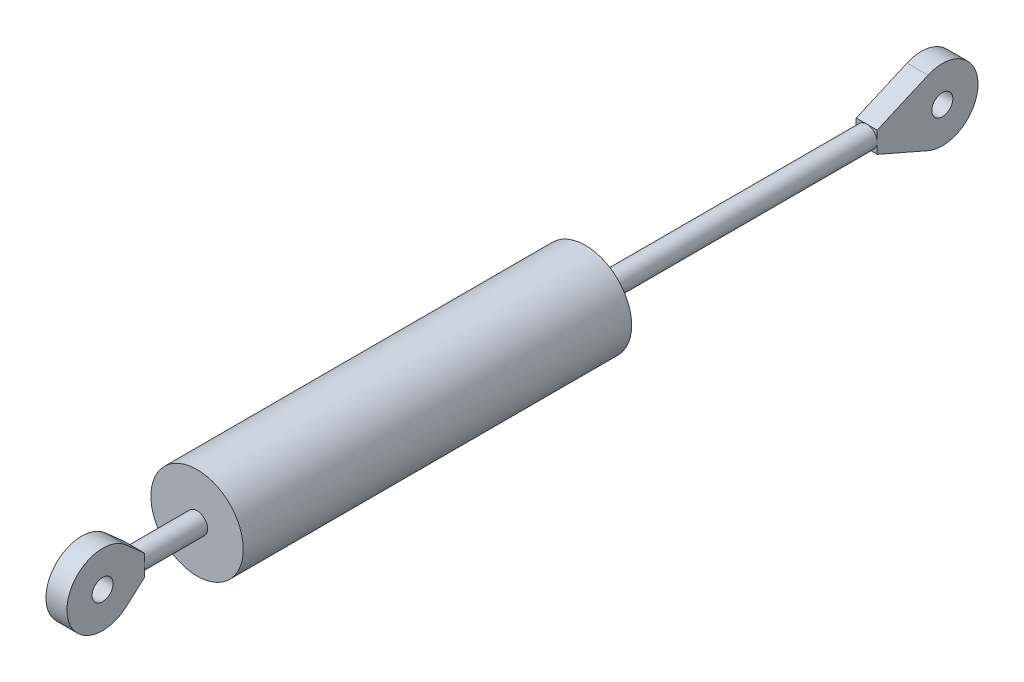
SolidWorks part; units mm, degrees
ref_plane "Front Plane" through (0, 0, 0) normal (0, 0, 1) x (1, 0, 0)
ref_plane "Top Plane" through (0, 0, 0) normal (0, 1, 0) x (1, 0, 0)
ref_plane "Right Plane" through (0, 0, 0) normal (1, 0, 0) x (0, 0, -1)
sketch "Sketch1" plane through (0, 0, 0) normal (1, 0, 0) x (0, 0, -1)
  line L0 (-46.25, 0) -> (46.25, 0)
  line L1 (-46.25, 11) -> (46.25, 11)
  line L2 (-46.25, 11) -> (-46.25, 0)
  line L4 (46.25, 11) -> (46.25, 0)
  line L5 (-46.25, 11) -> (0, 0) construction
  line L6 (0, 0) -> (46.25, 11) construction
  point P0 (0, 0)
  dimension "D1" = 92.5
  dimension "D2" = 11
revolve "Revolve1" add sketch "Sketch1" angle 360 about L0
sketch "Sketch2" plane through (0, 0, 46.25) normal (0, 0, 1) x (1, 0, 0)
  circle A0 centre (0, 0) radius 2.5
  dimension "D1" = 5
extrude "Boss-Extrude1" add sketch "Sketch2" along normal blind 15
sketch "Sketch3" plane through (0, 0, 0) normal (1, 0, 0) x (0, 0, -1)
  line L0 (-46.25, 11) -> (-46.25, -11) construction
  line L1 (-61.25, 2.5) -> (-65.6162, 6.3648)
  line L2 (-61.25, -2.5) -> (-65.6162, -6.3648)
  line L3 (-61.25, 2.5) -> (-61.25, -2.5)
  arc A0 (-65.6162, 6.3648) -> (-65.6162, -6.3648) centre (-71.25, 0) ccw
  circle A1 centre (-71.25, 0) radius 2.5
  dimension "D1" = 17
  dimension "D2" = 5
  dimension "D3" = 25
extrude "Boss-Extrude2" add sketch "Sketch3" along normal blind 2.5 and the other way blind 2.5
sketch "Sketch4" plane through (0, 0, -46.25) normal (0, 0, -1) x (-1, 0, 0)
  circle A0 centre (0, 0) radius 2.5
  dimension "D1" = 5
extrude "Boss-Extrude3" add sketch "Sketch4" along normal blind 67
sketch "Sketch5" plane through (0, 0, 0) normal (1, 0, 0) x (0, 0, -1)
  line L4 (46.25, -11) -> (46.25, 11) construction
  line L5 (0, 0) -> (112.0554, 0) construction
  line L6 (113.25, 2.5) -> (125.3449, 7.7881)
  line L7 (113.25, 2.5) -> (113.25, -2.5)
  line L8 (113.25, -2.5) -> (125.3449, -7.7881)
  circle A1 centre (128.75, 0) radius 2.5
  arc A2 (125.3449, -7.7881) -> (125.3449, 7.7881) centre (128.75, 0) ccw
  dimension "D1" = 8.5
  dimension "D2" = 5
  dimension "D3" = 82.5
extrude "Boss-Extrude4" add sketch "Sketch5" along normal blind 2.5 and the other way blind 2.5
